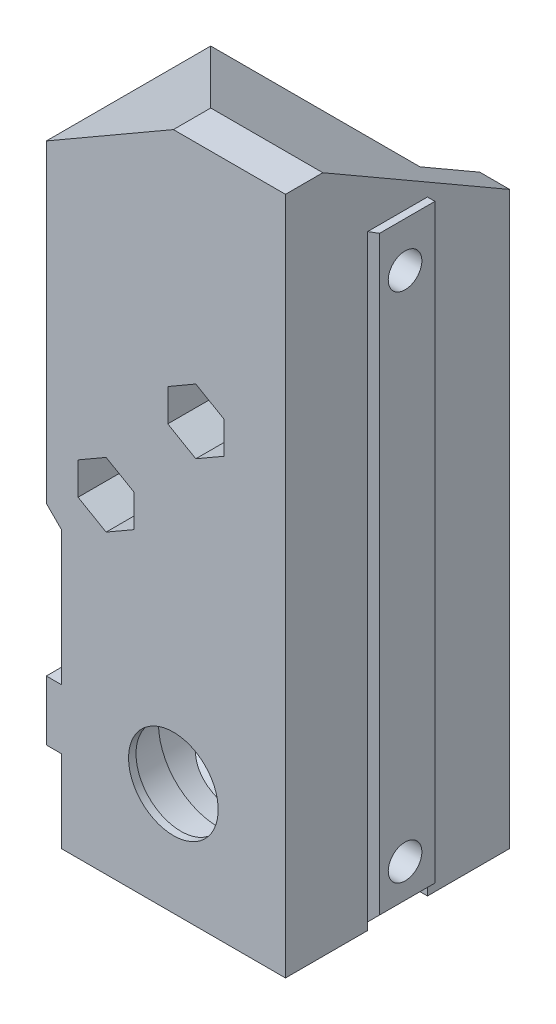
SolidWorks part; units mm, degrees
material "3D printed plastic"
ref_plane "Front Plane" through (0, 0, 0) normal (0, 0, 1) x (1, 0, 0)
ref_plane "Top Plane" through (0, 0, 0) normal (0, 1, 0) x (1, 0, 0)
ref_plane "Right Plane" through (0, 0, 0) normal (1, 0, 0) x (0, 0, -1)
sketch "Sketch1" plane through (0, 0, 0) normal (0, 0, 1) x (1, 0, 0)
  line L0 (-15, 71) -> (-17, 71)
  line L1 (-15, 71) -> (15, 71)
  line L2 (-15, 37) -> (-15, 0)
  line L3 (-15, 0) -> (15, 0)
  line L4 (15, 71) -> (15, 0)
  line L5 (-17, 71) -> (-17, 39)
  line L6 (-17, 39) -> (-15, 37)
  dimension "D1" = 30
  dimension "D2" = 71
  dimension "D3" = 45
  dimension "D4" = 2
  dimension "D5" = 37
extrude "Boss-Extrude1" add sketch "Sketch1" along normal mid plane 30
sketch "Sketch2" plane through (15, 0, 0) normal (1, 0, 0) x (0, 0, -1)
  line L0 (-15, 0) -> (15, 0) construction
  line L1 (-4, 0) -> (4, 0)
  line L2 (-4, 0) -> (-4, 1)
  line L3 (-4, 1) -> (4, 1)
  line L4 (4, 0) -> (4, 1)
  dimension "D1" = 8
  dimension "D2" = 1
extrude "Cut-Extrude1" cut sketch "Sketch2" against normal through all
sketch "Sketch3" plane through (15, 0, 0) normal (1, 0, 0) x (0, 0, -1)
  line L0 (-15, 71) -> (15, 71) construction
  line L1 (-4, 1) -> (4, 1)
  line L2 (-4, 1) -> (-4, 71)
  line L3 (-4, 71) -> (4, 71)
  line L4 (4, 1) -> (4, 71)
  line L6 (4, 0) -> (4, 1) construction
extrude "Boss-Extrude2" add sketch "Sketch3" along normal blind 1
chamfer "Chamfer2" distance 1 angle 45 1 edges at (16, 1, 0)
sketch "Sketch4" plane through (0, 0, -15) normal (0, 0, -1) x (-1, 0, 0)
  line L0 (-5, 36.5) -> (-5, 42)
  line L1 (-11, 71) -> (17, 71)
  line L2 (-11, 71) -> (-11, 51.1652)
  line L3 (-5, 36.5) -> (17, 36.5)
  line L4 (17, 71) -> (17, 36.5)
  line L5 (17, 71) -> (17, 39) construction
  line L6 (-15, 71) -> (17, 71) construction
  line L7 (-15, 0) -> (-15, 71) construction
  line L8 (15, 0) -> (-15, 0) construction
  arc A0 (-5, 42) -> (-11, 51.1652) centre (-1, 51.1652) cw
  dimension "D3" = 10
  dimension "D4" = 5.5
  dimension "D5" = 10
  dimension "D1" = 4
  dimension "D2" = 36.5
extrude "Cut-Extrude2" cut sketch "Sketch4" against normal blind 8
sketch "Sketch5" plane through (0, 0, -15) normal (0, 0, -1) x (-1, 0, 0)
  line L0 (0, 15) -> (0, 0) construction
  circle A0 centre (0, 15) radius 10
  dimension "D1" = 20
  dimension "D2" = 15
extrude "Cut-Extrude3" cut sketch "Sketch5" against normal blind 24
sketch "Sketch6" plane through (0, 0, 9) normal (0, 0, -1) x (-1, 0, 0)
  circle A0 centre (0, 15) radius 8
  dimension "D1" = 16
extrude "Cut-Extrude4" cut sketch "Sketch6" against normal blind 5
sketch "Sketch7" plane through (0, 0, 14) normal (0, 0, -1) x (-1, 0, 0)
  circle A0 centre (0, 15) radius 6
  dimension "D1" = 12
extrude "Cut-Extrude5" cut sketch "Sketch7" against normal through all
sketch "Sketch8" plane through (0, 0, -15) normal (0, 0, -1) x (-1, 0, 0)
  line L0 (17, 66) -> (-3, 66)
  line L1 (17, 39) -> (17, 71) construction
  line L2 (-10.4822, 57.984) -> (-7.4822, 14.484)
  line L3 (7.3261, 16.6057) -> (1.6739, 42.3943)
  line L4 (9, 51.5) -> (17, 51.5)
  line L5 (17, 71) -> (-11, 71) construction
  arc A0 (-3, 66) -> (-10.4822, 57.984) centre (-3, 58.5) ccw
  arc A1 (-7.4822, 14.484) -> (7.3261, 16.6057) centre (0, 15) ccw
  arc A2 (1.6739, 42.3943) -> (9, 51.5) centre (9, 44) cw
  circle A3 centre (0, 15) radius 8 construction
  dimension "D3" = 7.5
  dimension "D4" = 7.5
  dimension "D5" = 8
  dimension "D6" = 20
  dimension "D7" = 7.5
  dimension "D1" = 5
  dimension "D2" = 14.5
extrude "Cut-Extrude-Thin1" cut sketch "Sketch8" against normal mid plane 7.5 from offset 17 thin thin type two direction wall 2 second wall 2 offset against normal yes
sketch "Sketch9" plane through (0, 0, -15) normal (0, 0, -1) x (-1, 0, 0)
  circle A0 centre (-3, 58.5) radius 7
  circle A1 centre (9, 44) radius 7
  dimension "D1" = 14
extrude "Cut-Extrude6" cut sketch "Sketch9" against normal up to surface (20.75 mm away) up to face at (1.5833, 52.9927, 5.75)
sketch "Sketch11" plane through (0, 0, 5.75) normal (0, 0, -1) x (-1, 0, 0)
  circle A0 centre (-3, 58.5) radius 2
  circle A1 centre (9, 44) radius 2
  dimension "D1" = 4
extrude "Cut-Extrude7" cut sketch "Sketch11" against normal through all
sketch "Sketch12" plane through (0, 0, 5.75) normal (0, 0, -1) x (-1, 0, 0)
  circle A0 centre (-3, 58.5) radius 4.5
  circle A1 centre (9, 44) radius 4.5
  circle A2 centre (-3, 58.5) radius 2
  circle A3 centre (9, 44) radius 2
  circle A4 centre (-3, 58.5) radius 2 construction
  dimension "D1" = 9
extrude "Boss-Extrude4" add sketch "Sketch12" along normal blind 1.25
fillet "Fillet1" radius 2 8 edges at (6.0616, 22.9534, 2) (9.6923, 17.4615, 2) (8.3419, 20.5148, 5.75) (8.3419, 20.5148, -1.75) (-8.6112, 20.084, 2) (-6.4577, 22.6353, -1.75) (-6.4577, 22.6353, 5.75) (-3.5844, 24.3355, 2)
sketch "Sketch13" plane through (0, 0, 15) normal (0, 0, 1) x (1, 0, 0)
  line L1 (-9, 39.6699) -> (-5.25, 41.8349)
  line L2 (-5.25, 41.8349) -> (-5.25, 46.1651)
  line L3 (-5.25, 46.1651) -> (-9, 48.3301)
  line L4 (-9, 48.3301) -> (-12.75, 46.1651)
  line L5 (-12.75, 46.1651) -> (-12.75, 41.8349)
  line L6 (-12.75, 41.8349) -> (-9, 39.6699)
  line L7 (3, 54.1699) -> (6.75, 56.3349)
  line L8 (6.75, 56.3349) -> (6.75, 60.6651)
  line L9 (6.75, 60.6651) -> (3, 62.8301)
  line L10 (3, 62.8301) -> (-0.75, 60.6651)
  line L11 (-0.75, 60.6651) -> (-0.75, 56.3349)
  line L12 (-0.75, 56.3349) -> (3, 54.1699)
  circle A0 centre (-9, 44) radius 3.75 construction
  circle A1 centre (3, 58.5) radius 3.75 construction
  dimension "D1" = 7.5
extrude "Cut-Extrude8" cut sketch "Sketch13" against normal blind 8
other "Move Face1" face at (8.1, 71, -0.3) parameters "D1"=10
chamfer "Chamfer3" distance 1 angle 30 1 edges at (16, 41.5, 4) first distance on face at (15.5, 41.25, 4)
fillet "Fillet2" radius 1 8 edges at (-17, 51.5, -1.75) (-17, 49.5, 2) (-17, 51.5, 5.75) (-17, 53.5, 2) (-17, 66, -1.75) (-17, 64, 2) (-17, 66, 5.75) (-17, 68, 2)
sketch "Sketch16" plane through (0, 0, 0) normal (1, 0, 0) x (0, 0, -1)
  line L0 (15, 1) -> (0.0718, 5)
  line L1 (15, 36.5) -> (15, 0) construction
  line L2 (0.0718, 5) -> (0.0718, 15) construction
  line L3 (0.0718, 15) -> (15, 15)
  line L4 (15, 5) -> (15, 25) construction
  line L5 (15, 15) -> (15, 1)
  line L6 (-15, 0) -> (-4, 0) construction
  line L7 (-9, 5) -> (15, 5) construction
  line L8 (0.0718, 5) -> (-9, 7.4308)
  line L9 (-9, 7.4308) -> (-9, 15)
  line L10 (-9, 15) -> (0.0718, 15)
  line L11 (-9, 7) -> (-9, 23) construction
  dimension "D1" = 1
  dimension "D2" = 75
extrude "Cut-Extrude9" cut sketch "Sketch16" against normal mid plane 8
fillet "Fillet3" radius 2 5 edges at (-4, 5.8348, -5.978) (0, 5, -0.0718) (-4, 3.4174, -5.978) (4, 5.8348, -5.978) (4, 3.4174, -5.978)
sketch "Sketch17" plane through (-17, 0, 0) normal (-1, 0, 0) x (0, 0, 1)
  line L1 (15, 90.815) -> (15, 81)
  line L2 (15, 81) -> (-7, 81)
  line L3 (15, 90.815) -> (10, 90.815)
  line L4 (10, 90.815) -> (-7, 81)
  dimension "D1" = 30
  dimension "D2" = 5
extrude "Boss-Extrude5" add sketch "Sketch17" against normal up to surface (32 mm away) up to face at (15, 32.6, 8.4)
sketch "Sketch18" plane through (11, 0, 0) normal (-1, 0, 0) x (0, 0, 1)
  line L0 (-15, 81) -> (-7, 81)
  line L1 (-7, 81) -> (-15, 76.3812)
  line L2 (-15, 81) -> (-15, 51.1652) construction
  line L3 (-15, 76.3812) -> (-15, 81)
  line L5 (10, 90.815) -> (-7, 81) construction
extrude "Cut-Extrude10" cut sketch "Sketch18" against normal through all
sketch "Sketch19" plane through (0, 0, -7) normal (0, 0, -1) x (-1, 0, 0)
  line L0 (17, 81) -> (0, 90.815)
  line L2 (0, 90.815) -> (17, 90.815)
  line L3 (17, 90.815) -> (17, 81)
  line L4 (-15, 90.815) -> (17, 90.815) construction
  dimension "D1" = 60
extrude "Cut-Extrude11" cut sketch "Sketch19" against normal through all
chamfer "Chamfer4" distance 1.3 angle 45 1 edges at (5, 42, -11) first distance on face at (5, 39.25, -11)
sketch "Sketch20" plane through (-15, 0, 0) normal (-1, 0, 0) x (0, 0, 1)
  line L0 (15, 37) -> (15, 0) construction
  line L1 (15, 19) -> (10, 19)
  line L2 (15, 19) -> (15, 11)
  line L3 (15, 11) -> (10, 11)
  line L4 (10, 19) -> (10, 11)
  line L5 (-15, 36.5) -> (-15, 0) construction
  line L6 (-15, 19) -> (-10, 19) construction
  line L7 (-15, 19) -> (-15, 11) construction
  line L8 (-15, 11) -> (-10, 11) construction
  line L9 (-10, 19) -> (-10, 11) construction
  line L10 (10, 15) -> (-10, 15) construction
  line L11 (15, 0) -> (4, 0) construction
  dimension "D1" = 8
  dimension "D2" = 5
  dimension "D3" = 15
extrude "Boss-Extrude6" add sketch "Sketch20" along normal blind 2
sketch "Sketch21" plane through (-17, 0, 0) normal (-1, 0, 0) x (0, 0, 1)
  line L0 (0, 6.5) -> (0, 0) construction
  line L1 (0, 6.5) -> (0, 75) construction
  line L2 (15, 81) -> (-7, 81) construction
  circle A0 centre (0, 75) radius 2.25
  circle A1 centre (0, 6.5) radius 2.25
  dimension "D1" = 68.5
  dimension "D3" = 4.5
  dimension "D2" = 6
extrude "Cut-Extrude12" cut sketch "Sketch21" against normal through all
sketch "Sketch22" plane through (15, 0, 0) normal (1, 0, 0) x (0, 0, -1)
  circle A0 centre (0, 75) radius 4.75
  circle A1 centre (0, 6.5) radius 4.75
  dimension "D1" = 9.5
extrude "Cut-Extrude13" cut sketch "Sketch22" against normal through all from offset 2.8
